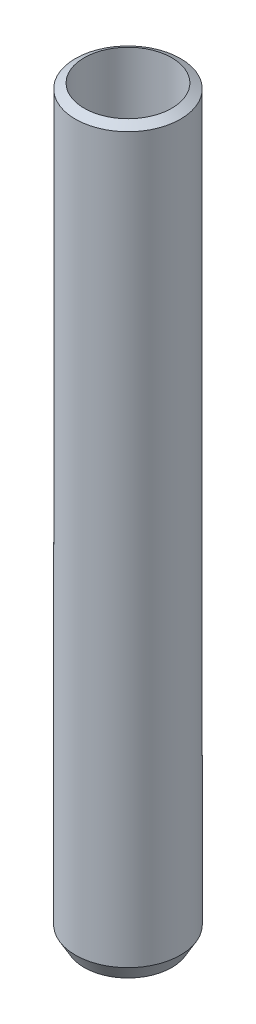
SolidWorks part; units mm, degrees
ref_plane "Front Plane" through (0, 0, 0) normal (0, 0, 1) x (1, 0, 0)
ref_plane "Top Plane" through (0, 0, 0) normal (0, 1, 0) x (1, 0, 0)
ref_plane "Right Plane" through (0, 0, 0) normal (1, 0, 0) x (0, 0, -1)
sketch "Sketch1" plane through (0, 0, 0) normal (0, 1, 0) x (1, 0, 0)
  circle A0 centre (0, 0) radius 30
  dimension "SHAFT_OD" = 60
extrude "Boss-Extrude1" add sketch "Sketch1" along normal blind 427.4855
sketch "Sketch2" plane through (0, 0, 0) normal (0, 1, 0) x (1, 0, 0)
  circle A0 centre (0, 0) radius 25.0045
  dimension "BORE_D" = 50.0089
extrude "Cut-Extrude1" cut sketch "Sketch2" along normal through all
chamfer "Chamfer1" distance 5.1967 angle 60 2 edges at (0, 427.4855, 30) (0, 0, 30) first distance on face at (0, 427.4855, 30) first distance on face at (0, 0, 25.0045)
